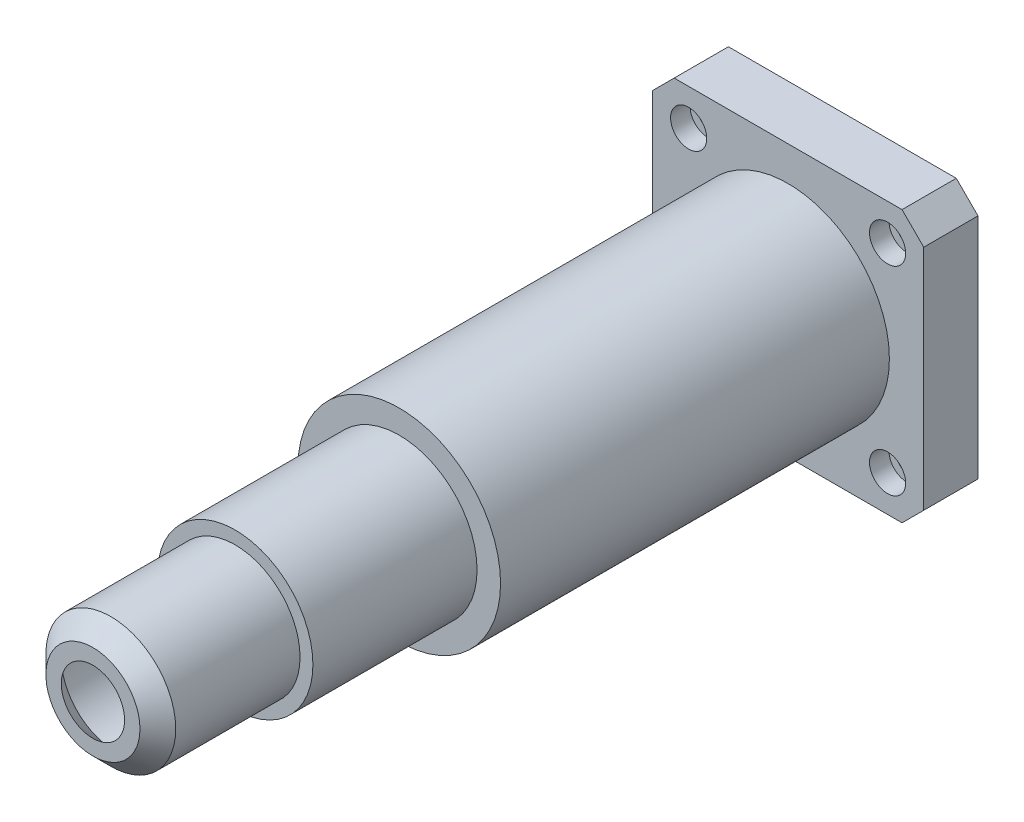
SolidWorks part; units mm, degrees
material "AISI Type 316L stainless steel"
ref_plane "Front Plane" through (0, 0, 0) normal (0, 0, 1) x (1, 0, 0)
ref_plane "Top Plane" through (0, 0, 0) normal (0, 1, 0) x (1, 0, 0)
ref_plane "Right Plane" through (0, 0, 0) normal (1, 0, 0) x (0, 0, -1)
sketch "Sketch1" plane through (0, 0, 0) normal (0, 0, 1) x (1, 0, 0)
  line L1 (-37.5, -37.5) -> (37.5, -37.5)
  line L2 (-37.5, -37.5) -> (-37.5, 37.5)
  line L3 (-37.5, 37.5) -> (37.5, 37.5)
  line L4 (37.5, -37.5) -> (37.5, 37.5)
  line L5 (-37.5, -37.5) -> (37.5, 37.5) construction
  line L6 (-37.5, 37.5) -> (37.5, -37.5) construction
  point P0 (0, 0)
  dimension "D1" = 75
extrude "Boss-Extrude1" add sketch "Sketch1" along normal blind 15
sketch "Sketch2" plane through (0, 0, 0) normal (0, 0, -1) x (-1, 0, 0)
  circle A0 centre (0, 0) radius 21
  dimension "D1" = 42
extrude "Boss-Extrude2" add sketch "Sketch2" along normal blind 5
sketch "Sketch3" plane through (0, 0, 0) normal (1, 0, 0) x (0, 0, -1)
  line L0 (-15, 28) -> (-122.5, 28)
  line L1 (-122.5, 28) -> (-122.5, 21.5)
  line L2 (-122.5, 21.5) -> (-167.8827, 21.5)
  line L3 (-167.8827, 21.5) -> (-167.8827, 17.9449)
  line L4 (-167.8827, 17.9449) -> (-202.2551, 17.9449)
  line L5 (-202.2551, 17.9449) -> (-207.2, 13)
  line L6 (-207.2, 13) -> (-207.2, 0)
  line L7 (-207.2, 0) -> (0, 0) construction
  line L8 (-15, 28) -> (-15, 0)
  line L9 (-15, -37.5) -> (-15, 37.5) construction
  line L10 (5, -21) -> (5, 21) construction
  line L11 (-207.2, 0) -> (-15, 0)
  dimension "D1" = 212.2
  dimension "D2" = 28
  dimension "D3" = 21.5
  dimension "D4" = 13
  dimension "D5" = 84.7
  dimension "D6" = 45
revolve "Revolve1" add sketch "Sketch3" angle 360 about L7
hole_wizard "CBORE for M5 Hex Socket Head Cap Screw1" positions "Sketch4" profile "Sketch5" counterbore size "M5" standard "ISO" end condition through all
sketch "Sketch4" plane through (0, 0, 15) normal (0, 0, 1) x (1, 0, 0)
  line L0 (37.5, 37.5) -> (-37.5, 37.5) construction
  line L1 (-37.5, 37.5) -> (-37.5, -37.5) construction
  point P0 (-27.5, 27.5)
  dimension "D1" = 10
  dimension "D2" = 10
sketch "Sketch5" plane through (-27.5, 27.5, 15) normal (1, 0, 0) x (0, -1, 0)
  line L0 (0, 0) -> (0, 20)
  line L1 (0, 20) -> (2.75, 20)
  line L3 (2.75, 20) -> (2.75, 5.4)
  line L4 (2.75, 5.4) -> (5, 5.4)
  line L5 (5, 5.4) -> (5, 0)
  line L7 (5, 0) -> (0, 0)
  line L11 (0, -6.35) -> (0, 107.95) construction
  dimension "Thru Hole Dia." = 5.5
  dimension "Thru Hole Depth" = 20
  dimension "C'Bore Dia." = 10
  dimension "C'Bore Depth" = 5.4
pattern_circular "CirPattern1" count 4 over 360 about axis through (0, 0, 15) along (0, 0, 1) of "CBORE for M5 Hex Socket Head Cap Screw1"
chamfer "Chamfer1" distance 6 angle 45 4 edges at (37.5, -37.5, 7.5) (-37.5, -37.5, 7.5) (37.5, 37.5, 7.5) (-37.5, 37.5, 7.5)
shell "Shell1" thickness 3 removed face at (-21, 0, -5) removed face at (13, 0, 207.2)
